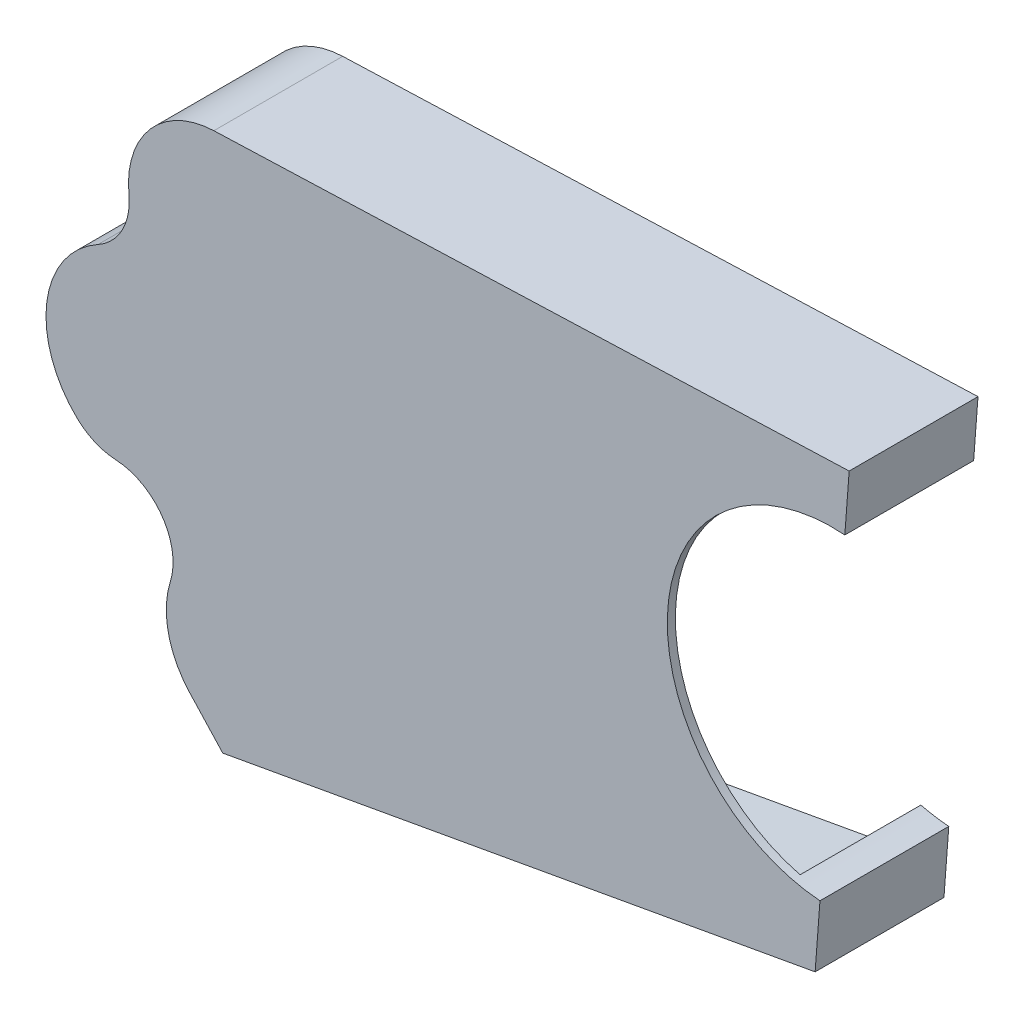
SolidWorks part; units mm, degrees
ref_plane "Front Plane" through (0, 0, 0) normal (0, 0, 1) x (1, 0, 0)
ref_plane "Top Plane" through (0, 0, 0) normal (0, 1, 0) x (1, 0, 0)
ref_plane "Right Plane" through (0, 0, 0) normal (1, 0, 0) x (0, 0, -1)
sketch "Sketch1" plane through (0, 0, 0) normal (0, 0, 1) x (1, 0, 0)
  line L8 (-119.5948, -74.4106) -> (-92.5405, -103.7404)
  line L9 (-119.5948, -74.4106) -> (-92.5405, -103.7404)
  line L10 (-71.3446, -104.5958) -> (-37.2211, -73.1197)
  line L11 (-71.3446, -104.5958) -> (-37.2211, -73.1197)
  line L16 (-27.1401, -68.1042) -> (68.9251, -50.7959)
  line L17 (-111.4072, -83.2869) -> (68.9251, -50.7959)
  line L18 (56.0883, 55.6165) -> (-113.6124, 49.4857)
  line L19 (56.0883, 55.6165) -> (-113.6124, 49.4857)
  line L20 (-114.4495, -69.6645) -> (-87.3952, -98.9943)
  line L21 (-114.4495, -69.6645) -> (-87.3952, -98.9943)
  line L22 (-76.0907, -99.4505) -> (-41.9673, -67.9744)
  line L23 (-76.0907, -99.4505) -> (-41.9673, -67.9744)
  line L28 (-28.3813, -61.2151) -> (67.6838, -43.9068)
  line L29 (-108.8671, -75.7165) -> (67.6838, -43.9068)
  line L30 (56.341, 48.621) -> (-113.3597, 42.4902)
  line L31 (56.341, 48.621) -> (-113.3597, 42.4902)
  line L32 (44.1846, 55.1864) -> (35.7309, -56.7765)
  line L33 (-27.1401, -68.1042) -> (68.9251, -50.7959) construction
  line L34 (-113.6124, 49.4857) -> (56.0883, 55.6165) construction
  line L35 (-111.6252, 43.3) -> (42.409, 31.6699) construction
  line L36 (36.6151, 47.9084) -> (29.1586, -50.848)
  arc A22 (-124.4228, -52.9336) -> (-137.9704, -33.4802) centre (-138.7403, -48.4604) ccw
  arc A23 (-124.4228, -52.9336) -> (-137.9704, -33.4802) centre (-138.7403, -48.4604) ccw
  arc A24 (-124.4228, -52.9336) -> (-119.5948, -74.4106) centre (-103.4238, -59.4942) ccw
  arc A25 (-124.4228, -52.9336) -> (-119.5948, -74.4106) centre (-103.4238, -59.4942) ccw
  arc A26 (-92.5405, -103.7404) -> (-71.3446, -104.5958) centre (-81.5148, -93.5701) ccw
  arc A27 (-92.5405, -103.7404) -> (-71.3446, -104.5958) centre (-81.5148, -93.5701) ccw
  arc A28 (-27.1401, -68.1042) -> (-37.2211, -73.1197) centre (-23.5699, -87.9191) ccw
  arc A29 (-27.1401, -68.1042) -> (-37.2211, -73.1197) centre (-23.5699, -87.9191) ccw
  arc A30 (68.9251, -50.7959) -> (91, -33.5) centre (63.6055, -21.2712) ccw
  arc A31 (68.9251, -50.7959) -> (91, -33.5) centre (63.6055, -21.2712) ccw
  arc A32 (91, -33.5) -> (80.2612, 44.7896) centre (22.6589, -2.9929) ccw
  arc A44 (91, -33.5) -> (80.2612, 44.7896) centre (22.6589, -2.9929) ccw
  arc A45 (80.2612, 44.7896) -> (56.0883, 55.6165) centre (57.1714, 25.636) ccw
  arc A46 (80.2612, 44.7896) -> (56.0883, 55.6165) centre (57.1714, 25.636) ccw
  arc A47 (-113.6124, 49.4857) -> (-134.7058, 25.2795) centre (-112.8181, 27.5) ccw
  arc A48 (-113.6124, 49.4857) -> (-134.7058, 25.2795) centre (-112.8181, 27.5) ccw
  arc A49 (-142.3827, 10.6321) -> (-134.7058, 25.2795) centre (-149.6292, 23.7656) ccw
  arc A50 (-142.3827, 10.6321) -> (-134.7058, 25.2795) centre (-149.6292, 23.7656) ccw
  arc A51 (-142.3827, 10.6321) -> (-147.5429, -29.3643) centre (-130.3054, -11.2571) ccw
  arc A52 (-142.3827, 10.6321) -> (-147.5429, -29.3643) centre (-130.3054, -11.2571) ccw
  arc A53 (-147.5429, -29.3643) -> (-137.9704, -33.4802) centre (-137.2004, -18.5) ccw
  arc A54 (-147.5429, -29.3643) -> (-137.9704, -33.4802) centre (-137.2004, -18.5) ccw
  arc A55 (-117.7413, -55.0211) -> (-137.611, -26.4895) centre (-138.7403, -48.4604) ccw
  arc A56 (-117.7413, -55.0211) -> (-137.611, -26.4895) centre (-138.7403, -48.4604) ccw
  arc A57 (-117.7413, -55.0211) -> (-114.4495, -69.6645) centre (-103.4238, -59.4942) ccw
  arc A58 (-117.7413, -55.0211) -> (-114.4495, -69.6645) centre (-103.4238, -59.4942) ccw
  arc A59 (-87.3952, -98.9943) -> (-76.0907, -99.4505) centre (-81.5148, -93.5701) ccw
  arc A60 (-87.3952, -98.9943) -> (-76.0907, -99.4505) centre (-81.5148, -93.5701) ccw
  arc A61 (-28.3813, -61.2151) -> (-41.9673, -67.9744) centre (-23.5699, -87.9191) ccw
  arc A62 (-28.3813, -61.2151) -> (-41.9673, -67.9744) centre (-23.5699, -87.9191) ccw
  arc A63 (67.6838, -43.9068) -> (84.608, -30.6466) centre (63.6055, -21.2712) ccw
  arc A73 (67.6838, -43.9068) -> (84.608, -30.6466) centre (63.6055, -21.2712) ccw
  arc A74 (84.608, -30.6466) -> (74.8736, 40.3204) centre (22.6589, -2.9929) ccw
  arc A75 (84.608, -30.6466) -> (74.8736, 40.3204) centre (22.6589, -2.9929) ccw
  arc A76 (74.8736, 40.3204) -> (56.341, 48.621) centre (57.1714, 25.636) ccw
  arc A77 (74.8736, 40.3204) -> (56.341, 48.621) centre (57.1714, 25.636) ccw
  arc A78 (-113.3597, 42.4902) -> (-127.7415, 25.986) centre (-112.8181, 27.5) ccw
  arc A79 (-113.3597, 42.4902) -> (-127.7415, 25.986) centre (-112.8181, 27.5) ccw
  arc A80 (-139.0011, 4.5031) -> (-127.7415, 25.986) centre (-149.6292, 23.7656) ccw
  arc A81 (-139.0011, 4.5031) -> (-127.7415, 25.986) centre (-149.6292, 23.7656) ccw
  arc A82 (-139.0011, 4.5031) -> (-142.7164, -24.2943) centre (-130.3054, -11.2571) ccw
  arc A83 (-139.0011, 4.5031) -> (-142.7164, -24.2943) centre (-130.3054, -11.2571) ccw
  arc A84 (-142.7164, -24.2943) -> (-137.611, -26.4895) centre (-137.2004, -18.5) ccw
  arc A85 (-142.7164, -24.2943) -> (-137.611, -26.4895) centre (-137.2004, -18.5) ccw
  circle A86 centre (40.0178, 0) radius 41
  arc A87 (28.1249, 38.1911) -> (0.393, 5.4659) centre (40.0178, 0) ccw construction
  dimension "D4" = 1
  dimension "D3" = 7
  dimension "D1" = 0
  dimension "D2" = 7
extrude "Boss-Extrude1" add sketch "Sketch1" along normal blind 30 contours A52 A54 A23 A25 L9 A27 L11 A29 L17 A31 A44 A46 L19 A48 A50 A85 A83 A81 A79 L31 A77 A75 A73 L29 A62 L23 A60 L21 A58 A56 | A62 L29 L21 L17 L23 | L29 A62 L23 L17 L32 | A86 L36 L29 L32 | A86 L32 L31 L36 region at (-122.5189, -63.7868, 0) region at (-72.9993, -72.6407, 0) region at (-2.1687, -60.1476, 0) region at (32.9424, -45.3152, 0) region at (39.8821, 44.4918, 0)
sketch "Sketch3" plane through (0, 0, 30) normal (0, 0, 1) x (1, 0, 0)
  line L0 (-65.2656, 44.2277) -> (121.4688, -34.2162)
  line L1 (-113.3597, 42.4902) -> (36.6151, 47.9084) construction
  line L2 (29.1586, -50.848) -> (-108.8671, -75.7165) construction
  dimension "D1" = 33
sketch "Sketch4" plane through (0, 0, 30) normal (0, 0, 1) x (1, 0, 0)
  line L21 (-113.3597, 42.4902) -> (36.6151, 47.9084)
  line L22 (36.6151, 47.9084) -> (36.0792, 40.8104)
  line L23 (43.1047, 40.8836) -> (44.1846, 55.1864)
  line L24 (44.1846, 55.1864) -> (-113.6124, 49.4857)
  line L25 (-119.5948, -74.4106) -> (-111.4072, -83.2869)
  line L26 (-111.4072, -83.2869) -> (35.7309, -56.7765)
  line L27 (35.7309, -56.7765) -> (36.9309, -40.8836)
  line L28 (29.9961, -39.7563) -> (29.1586, -50.848)
  line L29 (29.1586, -50.848) -> (-108.8671, -75.7165)
  line L30 (-108.8671, -75.7165) -> (-114.4495, -69.6645)
  line L31 (-113.3597, 42.4902) -> (36.6151, 47.9084)
  line L32 (36.6151, 47.9084) -> (36.0792, 40.8104)
  line L33 (43.1047, 40.8836) -> (44.1846, 55.1864)
  line L34 (44.1846, 55.1864) -> (-113.6124, 49.4857)
  line L35 (-119.5948, -74.4106) -> (-111.4072, -83.2869)
  line L36 (-111.4072, -83.2869) -> (35.7309, -56.7765)
  line L37 (35.7309, -56.7765) -> (36.9309, -40.8836)
  line L38 (29.9961, -39.7563) -> (29.1586, -50.848)
  line L39 (29.1586, -50.848) -> (-108.8671, -75.7165)
  line L40 (-108.8671, -75.7165) -> (-114.4495, -69.6645)
  circle A14 centre (40.0178, 0) radius 41
  arc A28 (-142.7164, -24.2943) -> (-137.611, -26.4895) centre (-137.2004, -18.5) ccw
  arc A29 (-139.0011, 4.5031) -> (-142.7164, -24.2943) centre (-130.3054, -11.2571) ccw
  arc A30 (-139.0011, 4.5031) -> (-127.7415, 25.986) centre (-149.6292, 23.7656) ccw
  arc A31 (-113.3597, 42.4902) -> (-127.7415, 25.986) centre (-112.8181, 27.5) ccw
  arc A32 (43.1047, 40.8836) -> (36.0792, 40.8104) centre (40.0178, 0) ccw
  arc A33 (-113.6124, 49.4857) -> (-134.7058, 25.2795) centre (-112.8181, 27.5) ccw
  arc A34 (-142.3827, 10.6321) -> (-134.7058, 25.2795) centre (-149.6292, 23.7656) ccw
  arc A35 (-142.3827, 10.6321) -> (-147.5429, -29.3643) centre (-130.3054, -11.2571) ccw
  arc A36 (-147.5429, -29.3643) -> (-137.9704, -33.4802) centre (-137.2004, -18.5) ccw
  arc A37 (-124.4228, -52.9336) -> (-137.9704, -33.4802) centre (-138.7403, -48.4604) ccw
  arc A38 (-124.4228, -52.9336) -> (-119.5948, -74.4106) centre (-103.4238, -59.4942) ccw
  arc A39 (29.9961, -39.7563) -> (36.9309, -40.8836) centre (40.0178, 0) ccw
  arc A40 (-117.7413, -55.0211) -> (-114.4495, -69.6645) centre (-103.4238, -59.4942) ccw
  arc A41 (-117.7413, -55.0211) -> (-137.611, -26.4895) centre (-138.7403, -48.4604) ccw
  arc A42 (-142.7164, -24.2943) -> (-137.611, -26.4895) centre (-137.2004, -18.5) ccw
  arc A43 (-139.0011, 4.5031) -> (-142.7164, -24.2943) centre (-130.3054, -11.2571) ccw
  arc A44 (-139.0011, 4.5031) -> (-127.7415, 25.986) centre (-149.6292, 23.7656) ccw
  arc A45 (-113.3597, 42.4902) -> (-127.7415, 25.986) centre (-112.8181, 27.5) ccw
  arc A46 (43.1047, 40.8836) -> (36.0792, 40.8104) centre (40.0178, 0) ccw
  arc A47 (-113.6124, 49.4857) -> (-134.7058, 25.2795) centre (-112.8181, 27.5) ccw
  arc A48 (-142.3827, 10.6321) -> (-134.7058, 25.2795) centre (-149.6292, 23.7656) ccw
  arc A49 (-142.3827, 10.6321) -> (-147.5429, -29.3643) centre (-130.3054, -11.2571) ccw
  arc A50 (-147.5429, -29.3643) -> (-137.9704, -33.4802) centre (-137.2004, -18.5) ccw
  arc A51 (-124.4228, -52.9336) -> (-137.9704, -33.4802) centre (-138.7403, -48.4604) ccw
  arc A52 (-124.4228, -52.9336) -> (-119.5948, -74.4106) centre (-103.4238, -59.4942) ccw
  arc A53 (29.9961, -39.7563) -> (36.9309, -40.8836) centre (40.0178, 0) ccw
  arc A54 (-117.7413, -55.0211) -> (-114.4495, -69.6645) centre (-103.4238, -59.4942) ccw
  arc A55 (-117.7413, -55.0211) -> (-137.611, -26.4895) centre (-138.7403, -48.4604) ccw
  arc M25 (-137.611, -26.4895) -> (-142.7164, -24.2943) centre (-137.2004, -18.5) cw
  arc M26 (-142.7164, -24.2943) -> (-139.0011, 4.5031) centre (-130.3054, -11.2571) cw
  arc M27 (-139.0011, 4.5031) -> (-127.7415, 25.986) centre (-149.6292, 23.7656) ccw
  arc M28 (-127.7415, 25.986) -> (-113.3597, 42.4902) centre (-112.8181, 27.5) cw
  line M29 (-113.3597, 42.4902) -> (36.6151, 47.9084)
  line M30 (36.6151, 47.9084) -> (36.0792, 40.8104)
  arc M31 (36.0792, 40.8104) -> (43.1047, 40.8836) centre (40.0178, 0) cw
  line M32 (43.1047, 40.8836) -> (44.1846, 55.1864)
  line M33 (44.1846, 55.1864) -> (-113.6124, 49.4857)
  arc M34 (-113.6124, 49.4857) -> (-134.7058, 25.2795) centre (-112.8181, 27.5) ccw
  arc M35 (-134.7058, 25.2795) -> (-142.3827, 10.6321) centre (-149.6292, 23.7656) cw
  arc M36 (-142.3827, 10.6321) -> (-147.5429, -29.3643) centre (-130.3054, -11.2571) ccw
  arc M37 (-147.5429, -29.3643) -> (-137.9704, -33.4802) centre (-137.2004, -18.5) ccw
  arc M38 (-137.9704, -33.4802) -> (-124.4228, -52.9336) centre (-138.7403, -48.4604) cw
  arc M39 (-124.4228, -52.9336) -> (-119.5948, -74.4106) centre (-103.4238, -59.4942) ccw
  line M40 (-119.5948, -74.4106) -> (-111.4072, -83.2869)
  line M41 (-111.4072, -83.2869) -> (35.7309, -56.7765)
  line M42 (35.7309, -56.7765) -> (36.9309, -40.8836)
  arc M43 (36.9309, -40.8836) -> (29.9961, -39.7563) centre (40.0178, 0) cw
  line M44 (29.9961, -39.7563) -> (29.1586, -50.848)
  line M45 (29.1586, -50.848) -> (-108.8671, -75.7165)
  line M46 (-108.8671, -75.7165) -> (-114.4495, -69.6645)
  arc M47 (-114.4495, -69.6645) -> (-117.7413, -55.0211) centre (-103.4238, -59.4942) cw
  arc M48 (-117.7413, -55.0211) -> (-137.611, -26.4895) centre (-138.7403, -48.4604) ccw
  dimension "D1" = 0
extrude "Boss-Extrude2" add sketch "Sketch4" along normal blind 2 contours A14 M30 M29 M28 M27 M26 M25 M48 M47 M46 M45 M44 | M48 M25 M26 M27 M28 M29 M30 M31 M32 M33 M34 M35 M36 M37 M38 M39 M40 M41 M42 M43 M44 M45 M46 M47 region at (-125.9577, 38.9499, 30) region at (-60.3524, -9.964, 30)
